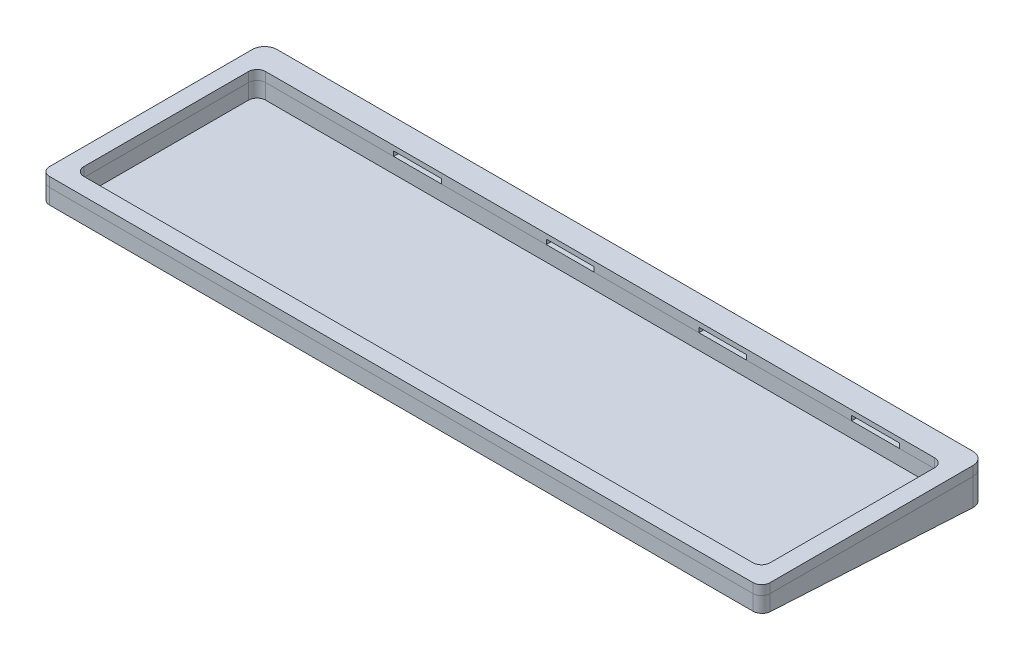
SolidWorks part; units mm, degrees
ref_plane "Front Plane" through (0, 0, 0) normal (0, 0, 1) x (1, 0, 0)
ref_plane "Top Plane" through (0, 0, 0) normal (0, 1, 0) x (1, 0, 0)
ref_plane "Right Plane" through (0, 0, 0) normal (1, 0, 0) x (0, 0, -1)
sketch "Sketch1" plane through (0, 0, 0) normal (0, 1, 0) x (1, 0, 0)
  line L0 (-179.825, 47.6224) -> (-179.825, 47.625)
  line L1 (-179.8217, 47.625) -> (179.825, 47.625)
  line L2 (-179.825, 47.6224) -> (-179.825, -47.625)
  line L3 (-179.825, -47.625) -> (179.825, -47.625)
  line L4 (179.825, 47.625) -> (179.825, -47.625)
  line L5 (-179.825, 47.625) -> (179.825, -47.625) construction
  line L6 (-179.825, -47.625) -> (179.825, 47.625) construction
  line L7 (-179.825, 47.625) -> (-179.8217, 47.625)
  circle A4 centre (157.075, 19.175) radius 1.1
  circle A5 centre (136.925, -16.775) radius 1.1
  circle A6 centre (-153.475, 33.725) radius 1.1
  circle A7 centre (17.925, 22.275) radius 1.1
  circle A8 centre (17.875, -35.075) radius 1.1
  circle A9 centre (-130.375, -35.725) radius 1.1
  point P0 (0, 0)
  dimension "D4" = 2.2
  dimension "D7" = 2.2
  dimension "D8" = 2.2
  dimension "D9" = 2.2
  dimension "D10" = 2.2
  dimension "D11" = 2.2
  dimension "D1" = 359.65
  dimension "D2" = 95.25
  dimension "D5" = 22.75
  dimension "D6" = 28.45
  dimension "D12" = 42.9
  dimension "D13" = 30.85
  dimension "D14" = 25.35
  dimension "D15" = 161.9
  dimension "D16" = 12.55
  dimension "D17" = 161.95
  dimension "D18" = 11.9
  dimension "D19" = 49.45
  dimension "D20" = 13.9
  dimension "D21" = 26.35
sketch "Sketch2" plane through (0, 0, 0) normal (0, 1, 0) x (1, 0, 0)
  line L0 (-188.825, 54.625) -> (-188.825, 60.625)
  line L1 (-188.825, 60.625) -> (-182.825, 60.625)
  line L4 (-179.825, 46.625) -> (-179.825, -46.625)
  line L5 (-178.825, -47.625) -> (178.825, -47.625)
  line L6 (179.825, 46.625) -> (179.825, -46.625)
  line L7 (-178.825, 47.625) -> (178.825, 47.625)
  line L8 (-179.825, 46.625) -> (-179.825, 47.625)
  line L9 (-182.825, 60.625) -> (188.825, 60.625)
  line L10 (-188.825, 54.625) -> (-188.825, -56.625)
  line L11 (-188.825, -56.625) -> (188.825, -56.625)
  line L12 (188.825, 60.625) -> (188.825, -56.625)
  line L13 (-179.825, 47.625) -> (-178.825, 47.625)
  line L14 (-179.825, -46.625) -> (-179.825, -47.625)
  line L15 (-179.825, -47.625) -> (-178.825, -47.625)
  line L16 (178.825, -47.625) -> (179.825, -47.625)
  line L17 (179.825, -47.625) -> (179.825, -46.625)
  line L18 (178.825, 47.625) -> (179.825, 47.625)
  line L19 (179.825, 47.625) -> (179.825, 46.625)
  circle A0 centre (157.075, 19.175) radius 1.1 construction
  circle A1 centre (136.925, -16.775) radius 1.1 construction
  circle A2 centre (17.875, -35.075) radius 1.1 construction
  circle A3 centre (17.925, 22.275) radius 1.1 construction
  circle A4 centre (-153.475, 33.725) radius 1.1 construction
  circle A5 centre (-130.375, -35.725) radius 1.1 construction
  circle A10 centre (157.075, 19.175) radius 1.1
  circle A11 centre (136.925, -16.775) radius 1.1
  circle A12 centre (17.875, -35.075) radius 1.1
  circle A13 centre (17.925, 22.275) radius 1.1
  circle A14 centre (-153.475, 33.725) radius 1.1
  circle A15 centre (-130.375, -35.725) radius 1.1
  point P30 (0, 0)
  dimension "D1" = 13
  dimension "D2" = 9
  dimension "D3" = 9
  dimension "D4" = 9
extrude "Boss-Extrude1" add sketch "Sketch2" along normal blind 13
sketch "Sketch4" plane through (0, 0, 0) normal (0, -1, 0) x (1, 0, 0)
  line L1 (-188.825, -60.625) -> (188.825, -60.625) construction
  line L3 (-188.825, 56.625) -> (188.825, 56.625) construction
  line L4 (-179.825, 47.625) -> (-179.825, -47.625)
  line L5 (179.825, 47.625) -> (-179.825, 47.625)
  line L6 (179.825, -47.625) -> (179.825, 47.625)
  line L7 (-179.825, -47.625) -> (179.825, -47.625)
  line L8 (-179.825, 47.625) -> (-179.825, -47.625)
  line L10 (179.825, -47.625) -> (179.825, 47.625)
  line L11 (-179.825, -47.625) -> (179.825, -47.625)
  line L12 (188.825, -60.625) -> (188.825, 56.625)
  line L13 (-188.825, -60.625) -> (188.825, -60.625)
  line L14 (-188.825, -60.625) -> (-188.825, 56.625)
  line L15 (-188.825, 56.625) -> (188.825, 56.625)
  line M10 (-179.825, -47.625) -> (-179.825, 47.625)
  line M12 (-179.825, 47.625) -> (179.825, 47.625)
  line M14 (179.825, 47.625) -> (179.825, -47.625)
  line M16 (179.825, -47.625) -> (-179.825, -47.625)
  line M17 (-188.825, 56.625) -> (-188.825, -60.625)
  line M19 (-188.825, -60.625) -> (188.825, -60.625)
  line M21 (188.825, -60.625) -> (188.825, 56.625)
  line M23 (188.825, 56.625) -> (-188.825, 56.625)
  dimension "D1" = 0
extrude "Boss-Extrude3" add sketch "Sketch4" along normal blind 10.5 contours M17 M19 M21 M23 M16 M10 M12 M14 | M16 M14 M12 M10 region at (0, 0, 0) region at (0, 0, -56.6707)
sketch "Sketch12" plane through (-188.825, 0, 0) normal (-1, 0, 0) x (0, 0, 1)
  line L0 (-60.625, 0) -> (56.625, 0) construction
  line L1 (-60.625, 13) -> (-60.625, -10.5) construction
  line L2 (56.625, 13) -> (56.625, -10.5) construction
  line L3 (56.625, -10.5) -> (-60.625, -10.5) construction
  line L4 (-60.625, -10.5) -> (-60.625, -6.5)
  line L5 (-60.625, -6.5) -> (56.625, 0)
  line L6 (56.625, 0) -> (56.625, -10.5)
  line L7 (56.625, -10.5) -> (-60.625, -10.5)
  dimension "D1" = 10.5
  dimension "D2" = 4
extrude "Cut-Extrude3" cut sketch "Sketch12" against normal blind 400
sketch "Sketch9" plane through (0, 0, 0) normal (0, 1, 0) x (1, 0, 0)
  line L0 (-121.9453, 45.1) -> (-108.9453, 45.1)
  line L1 (-121.9453, 31.1) -> (-108.9453, 31.1)
  line L2 (-122.4453, 44.6) -> (-122.4453, 31.6)
  line L3 (-108.4453, 44.6) -> (-108.4453, 31.6)
  line L4 (-102.8953, 45.1) -> (-89.8953, 45.1)
  line L5 (-102.8953, 31.1) -> (-89.8953, 31.1)
  line L6 (-103.3953, 44.6) -> (-103.3953, 31.6)
  line L7 (-89.3953, 44.6) -> (-89.3953, 31.6)
  line L8 (-83.8453, 45.1) -> (-70.8453, 45.1)
  line L9 (-83.8453, 31.1) -> (-70.8453, 31.1)
  line L10 (-84.3453, 44.6) -> (-84.3453, 31.6)
  line L11 (-70.3453, 44.6) -> (-70.3453, 31.6)
  line L12 (-64.7953, 45.1) -> (-51.7953, 45.1)
  line L13 (-64.7953, 31.1) -> (-51.7953, 31.1)
  line L14 (-65.2953, 44.6) -> (-65.2953, 31.6)
  line L15 (-51.2953, 44.6) -> (-51.2953, 31.6)
  line L16 (-45.7453, 45.1) -> (-32.7453, 45.1)
  line L17 (-45.7453, 31.1) -> (-32.7453, 31.1)
  line L18 (-46.2453, 44.6) -> (-46.2453, 31.6)
  line L19 (-32.2453, 44.6) -> (-32.2453, 31.6)
  line L20 (-26.6953, 45.1) -> (-13.6953, 45.1)
  line L21 (-26.6953, 31.1) -> (-13.6953, 31.1)
  line L22 (-27.1953, 44.6) -> (-27.1953, 31.6)
  line L23 (-13.1953, 44.6) -> (-13.1953, 31.6)
  line L24 (-7.6453, 45.1) -> (5.3547, 45.1)
  line L25 (-7.6453, 31.1) -> (5.3547, 31.1)
  line L26 (-8.1453, 44.6) -> (-8.1453, 31.6)
  line L27 (5.8547, 44.6) -> (5.8547, 31.6)
  line L28 (11.4047, 45.1) -> (24.4047, 45.1)
  line L29 (11.4047, 31.1) -> (24.4047, 31.1)
  line L30 (10.9047, 44.6) -> (10.9047, 31.6)
  line L31 (24.9047, 44.6) -> (24.9047, 31.6)
  line L32 (30.4547, 45.1) -> (43.4547, 45.1)
  line L33 (30.4547, 31.1) -> (43.4547, 31.1)
  line L34 (29.9547, 44.6) -> (29.9547, 31.6)
  line L35 (43.9547, 44.6) -> (43.9547, 31.6)
  line L36 (49.5047, 45.1) -> (62.5047, 45.1)
  line L37 (49.5047, 31.1) -> (62.5047, 31.1)
  line L38 (49.0047, 44.6) -> (49.0047, 31.6)
  line L39 (63.0047, 44.6) -> (63.0047, 31.6)
  line L40 (68.5547, 45.1) -> (81.5547, 45.1)
  line L41 (68.5547, 31.1) -> (81.5547, 31.1)
  line L42 (68.0547, 44.6) -> (68.0547, 31.6)
  line L43 (82.0547, 44.6) -> (82.0547, 31.6)
  line L44 (87.6047, 45.1) -> (100.6047, 45.1)
  line L45 (87.6047, 31.1) -> (100.6047, 31.1)
  line L46 (87.1047, 44.6) -> (87.1047, 31.6)
  line L47 (101.1047, 44.6) -> (101.1047, 31.6)
  line L48 (106.6547, 45.1) -> (119.6547, 45.1)
  line L49 (106.6547, 31.1) -> (119.6547, 31.1)
  line L50 (106.1547, 44.6) -> (106.1547, 31.6)
  line L51 (120.1547, 44.6) -> (120.1547, 31.6)
  line L52 (135.2297, 45.1) -> (148.2297, 45.1)
  line L53 (135.2297, 31.1) -> (148.2297, 31.1)
  line L54 (134.7297, 44.6) -> (134.7297, 31.6)
  line L55 (148.7297, 44.6) -> (148.7297, 31.6)
  line L56 (150.6677, 44.1) -> (156.6677, 44.1)
  line L57 (150.6677, 29.1) -> (156.6677, 29.1)
  line L58 (150.1677, 43.6) -> (150.1677, 29.6)
  line L59 (157.1677, 43.6) -> (157.1677, 29.6)
  line L60 (126.7917, 44.1) -> (132.7917, 44.1)
  line L61 (126.7917, 29.1) -> (132.7917, 29.1)
  line L62 (126.2917, 43.6) -> (126.2917, 29.6)
  line L63 (133.2917, 43.6) -> (133.2917, 29.6)
  line L64 (163.8047, 45.1) -> (176.8047, 45.1)
  line L65 (163.8047, 31.1) -> (176.8047, 31.1)
  line L66 (163.3047, 44.6) -> (163.3047, 31.6)
  line L67 (177.3047, 44.6) -> (177.3047, 31.6)
  line L68 (-117.1828, 26.05) -> (-104.1828, 26.05)
  line L69 (-117.1828, 12.05) -> (-104.1828, 12.05)
  line L70 (-117.6828, 25.55) -> (-117.6828, 12.55)
  line L71 (-103.6828, 25.55) -> (-103.6828, 12.55)
  line L72 (-93.3703, 26.05) -> (-80.3703, 26.05)
  line L73 (-93.3703, 12.05) -> (-80.3703, 12.05)
  line L74 (-93.8703, 25.55) -> (-93.8703, 12.55)
  line L75 (-79.8703, 25.55) -> (-79.8703, 12.55)
  line L76 (-74.3203, 26.05) -> (-61.3203, 26.05)
  line L77 (-74.3203, 12.05) -> (-61.3203, 12.05)
  line L78 (-74.8203, 25.55) -> (-74.8203, 12.55)
  line L79 (-60.8203, 25.55) -> (-60.8203, 12.55)
  line L80 (-55.2703, 26.05) -> (-42.2703, 26.05)
  line L81 (-55.2703, 12.05) -> (-42.2703, 12.05)
  line L82 (-55.7703, 25.55) -> (-55.7703, 12.55)
  line L83 (-41.7703, 25.55) -> (-41.7703, 12.55)
  line L84 (-36.2203, 26.05) -> (-23.2203, 26.05)
  line L85 (-36.2203, 12.05) -> (-23.2203, 12.05)
  line L86 (-36.7203, 25.55) -> (-36.7203, 12.55)
  line L87 (-22.7203, 25.55) -> (-22.7203, 12.55)
  line L88 (-17.1703, 26.05) -> (-4.1703, 26.05)
  line L89 (-17.1703, 12.05) -> (-4.1703, 12.05)
  line L90 (-17.6703, 25.55) -> (-17.6703, 12.55)
  line L91 (-3.6703, 25.55) -> (-3.6703, 12.55)
  line L92 (1.8797, 26.05) -> (14.8797, 26.05)
  line L93 (1.8797, 12.05) -> (14.8797, 12.05)
  line L94 (1.3797, 25.55) -> (1.3797, 12.55)
  line L95 (15.3797, 25.55) -> (15.3797, 12.55)
  line L96 (20.9297, 26.05) -> (33.9297, 26.05)
  line L97 (20.9297, 12.05) -> (33.9297, 12.05)
  line L98 (20.4297, 25.55) -> (20.4297, 12.55)
  line L99 (34.4297, 25.55) -> (34.4297, 12.55)
  line L100 (39.9797, 26.05) -> (52.9797, 26.05)
  line L101 (39.9797, 12.05) -> (52.9797, 12.05)
  line L102 (39.4797, 25.55) -> (39.4797, 12.55)
  line L103 (53.4797, 25.55) -> (53.4797, 12.55)
  line L104 (59.0297, 26.05) -> (72.0297, 26.05)
  line L105 (59.0297, 12.05) -> (72.0297, 12.05)
  line L106 (58.5297, 25.55) -> (58.5297, 12.55)
  line L107 (72.5297, 25.55) -> (72.5297, 12.55)
  line L108 (78.0797, 26.05) -> (91.0797, 26.05)
  line L109 (78.0797, 12.05) -> (91.0797, 12.05)
  line L110 (77.5797, 25.55) -> (77.5797, 12.55)
  line L111 (91.5797, 25.55) -> (91.5797, 12.55)
  line L112 (97.1297, 26.05) -> (110.1297, 26.05)
  line L113 (97.1297, 12.05) -> (110.1297, 12.05)
  line L114 (96.6297, 25.55) -> (96.6297, 12.55)
  line L115 (110.6297, 25.55) -> (110.6297, 12.55)
  line L116 (116.1797, 26.05) -> (129.1797, 26.05)
  line L117 (116.1797, 12.05) -> (129.1797, 12.05)
  line L118 (115.6797, 25.55) -> (115.6797, 12.55)
  line L119 (129.6797, 25.55) -> (129.6797, 12.55)
  line L120 (139.9922, 26.05) -> (152.9922, 26.05)
  line L121 (139.9922, 12.05) -> (152.9922, 12.05)
  line L122 (139.4922, 25.55) -> (139.4922, 12.55)
  line L123 (153.4922, 25.55) -> (153.4922, 12.55)
  line L124 (163.8047, 26.05) -> (176.8047, 26.05)
  line L125 (163.8047, 12.05) -> (176.8047, 12.05)
  line L126 (163.3047, 25.55) -> (163.3047, 12.55)
  line L127 (177.3047, 25.55) -> (177.3047, 12.55)
  line L128 (-114.8016, 7) -> (-101.8016, 7)
  line L129 (-114.8016, -7) -> (-101.8016, -7)
  line L130 (-115.3016, 6.5) -> (-115.3016, -6.5)
  line L131 (-101.3016, 6.5) -> (-101.3016, -6.5)
  line L132 (-88.6078, 7) -> (-75.6078, 7)
  line L133 (-88.6078, -7) -> (-75.6078, -7)
  line L134 (-89.1078, 6.5) -> (-89.1078, -6.5)
  line L135 (-75.1078, 6.5) -> (-75.1078, -6.5)
  line L136 (-69.5578, 7) -> (-56.5578, 7)
  line L137 (-69.5578, -7) -> (-56.5578, -7)
  line L138 (-70.0578, 6.5) -> (-70.0578, -6.5)
  line L139 (-56.0578, 6.5) -> (-56.0578, -6.5)
  line L140 (-50.5078, 7) -> (-37.5078, 7)
  line L141 (-50.5078, -7) -> (-37.5078, -7)
  line L142 (-51.0078, 6.5) -> (-51.0078, -6.5)
  line L143 (-37.0078, 6.5) -> (-37.0078, -6.5)
  line L144 (-31.4578, 7) -> (-18.4578, 7)
  line L145 (-31.4578, -7) -> (-18.4578, -7)
  line L146 (-31.9578, 6.5) -> (-31.9578, -6.5)
  line L147 (-17.9578, 6.5) -> (-17.9578, -6.5)
  line L148 (-12.4078, 7) -> (0.5922, 7)
  line L149 (-12.4078, -7) -> (0.5922, -7)
  line L150 (-12.9078, 6.5) -> (-12.9078, -6.5)
  line L151 (1.0922, 6.5) -> (1.0922, -6.5)
  line L152 (6.6422, 7) -> (19.6422, 7)
  line L153 (6.6422, -7) -> (19.6422, -7)
  line L154 (6.1422, 6.5) -> (6.1422, -6.5)
  line L155 (20.1422, 6.5) -> (20.1422, -6.5)
  line L156 (25.6922, 7) -> (38.6922, 7)
  line L157 (25.6922, -7) -> (38.6922, -7)
  line L158 (25.1922, 6.5) -> (25.1922, -6.5)
  line L159 (39.1922, 6.5) -> (39.1922, -6.5)
  line L160 (44.7422, 7) -> (57.7422, 7)
  line L161 (44.7422, -7) -> (57.7422, -7)
  line L162 (44.2422, 6.5) -> (44.2422, -6.5)
  line L163 (58.2422, 6.5) -> (58.2422, -6.5)
  line L164 (63.7922, 7) -> (76.7922, 7)
  line L165 (63.7922, -7) -> (76.7922, -7)
  line L166 (63.2922, 6.5) -> (63.2922, -6.5)
  line L167 (77.2922, 6.5) -> (77.2922, -6.5)
  line L168 (82.8422, 7) -> (95.8422, 7)
  line L169 (82.8422, -7) -> (95.8422, -7)
  line L170 (82.3422, 6.5) -> (82.3422, -6.5)
  line L171 (96.3422, 6.5) -> (96.3422, -6.5)
  line L172 (101.8922, 7) -> (114.8922, 7)
  line L173 (101.8922, -7) -> (114.8922, -7)
  line L174 (101.3922, 6.5) -> (101.3922, -6.5)
  line L175 (115.3922, 6.5) -> (115.3922, -6.5)
  line L176 (132.8484, 7) -> (145.8484, 7)
  line L177 (132.8484, -7) -> (145.8484, -7)
  line L178 (132.3484, 6.5) -> (132.3484, -6.5)
  line L179 (146.3484, 6.5) -> (146.3484, -6.5)
  line L180 (148.2864, 6) -> (154.2864, 6)
  line L181 (148.2864, -9) -> (154.2864, -9)
  line L182 (147.7864, 5.5) -> (147.7864, -8.5)
  line L183 (154.7864, 5.5) -> (154.7864, -8.5)
  line L184 (124.4104, 6) -> (130.4104, 6)
  line L185 (124.4104, -9) -> (130.4104, -9)
  line L186 (123.9104, 5.5) -> (123.9104, -8.5)
  line L187 (130.9104, 5.5) -> (130.9104, -8.5)
  line L188 (163.8047, 7) -> (176.8047, 7)
  line L189 (163.8047, -7) -> (176.8047, -7)
  line L190 (163.3047, 6.5) -> (163.3047, -6.5)
  line L191 (177.3047, 6.5) -> (177.3047, -6.5)
  line L192 (-110.0391, -12.05) -> (-97.0391, -12.05)
  line L193 (-110.0391, -26.05) -> (-97.0391, -26.05)
  line L194 (-110.5391, -12.55) -> (-110.5391, -25.55)
  line L195 (-96.5391, -12.55) -> (-96.5391, -25.55)
  line L196 (-94.6011, -13.05) -> (-88.6011, -13.05)
  line L197 (-94.6011, -28.05) -> (-88.6011, -28.05)
  line L198 (-95.1011, -13.55) -> (-95.1011, -27.55)
  line L199 (-88.1011, -13.55) -> (-88.1011, -27.55)
  line L200 (-118.4771, -13.05) -> (-112.4771, -13.05)
  line L201 (-118.4771, -28.05) -> (-112.4771, -28.05)
  line L202 (-118.9771, -13.55) -> (-118.9771, -27.55)
  line L203 (-111.9771, -13.55) -> (-111.9771, -27.55)
  line L204 (-79.0828, -12.05) -> (-66.0828, -12.05)
  line L205 (-79.0828, -26.05) -> (-66.0828, -26.05)
  line L206 (-79.5828, -12.55) -> (-79.5828, -25.55)
  line L207 (-65.5828, -12.55) -> (-65.5828, -25.55)
  line L208 (-60.0328, -12.05) -> (-47.0328, -12.05)
  line L209 (-60.0328, -26.05) -> (-47.0328, -26.05)
  line L210 (-60.5328, -12.55) -> (-60.5328, -25.55)
  line L211 (-46.5328, -12.55) -> (-46.5328, -25.55)
  line L212 (-40.9828, -12.05) -> (-27.9828, -12.05)
  line L213 (-40.9828, -26.05) -> (-27.9828, -26.05)
  line L214 (-41.4828, -12.55) -> (-41.4828, -25.55)
  line L215 (-27.4828, -12.55) -> (-27.4828, -25.55)
  line L216 (-21.9328, -12.05) -> (-8.9328, -12.05)
  line L217 (-21.9328, -26.05) -> (-8.9328, -26.05)
  line L218 (-22.4328, -12.55) -> (-22.4328, -25.55)
  line L219 (-8.4328, -12.55) -> (-8.4328, -25.55)
  line L220 (-2.8828, -12.05) -> (10.1172, -12.05)
  line L221 (-2.8828, -26.05) -> (10.1172, -26.05)
  line L222 (-3.3828, -12.55) -> (-3.3828, -25.55)
  line L223 (10.6172, -12.55) -> (10.6172, -25.55)
  line L224 (16.1672, -12.05) -> (29.1672, -12.05)
  line L225 (16.1672, -26.05) -> (29.1672, -26.05)
  line L226 (15.6672, -12.55) -> (15.6672, -25.55)
  line L227 (29.6672, -12.55) -> (29.6672, -25.55)
  line L228 (35.2172, -12.05) -> (48.2172, -12.05)
  line L229 (35.2172, -26.05) -> (48.2172, -26.05)
  line L230 (34.7172, -12.55) -> (34.7172, -25.55)
  line L231 (48.7172, -12.55) -> (48.7172, -25.55)
  line L232 (54.2672, -12.05) -> (67.2672, -12.05)
  line L233 (54.2672, -26.05) -> (67.2672, -26.05)
  line L234 (53.7672, -12.55) -> (53.7672, -25.55)
  line L235 (67.7672, -12.55) -> (67.7672, -25.55)
  line L236 (73.3172, -12.05) -> (86.3172, -12.05)
  line L237 (73.3172, -26.05) -> (86.3172, -26.05)
  line L238 (72.8172, -12.55) -> (72.8172, -25.55)
  line L239 (86.8172, -12.55) -> (86.8172, -25.55)
  line L240 (92.3672, -12.05) -> (105.3672, -12.05)
  line L241 (92.3672, -26.05) -> (105.3672, -26.05)
  line L242 (91.8672, -12.55) -> (91.8672, -25.55)
  line L243 (105.8672, -12.55) -> (105.8672, -25.55)
  line L244 (118.5609, -12.05) -> (131.5609, -12.05)
  line L245 (118.5609, -26.05) -> (131.5609, -26.05)
  line L246 (118.0609, -12.55) -> (118.0609, -25.55)
  line L247 (132.0609, -12.55) -> (132.0609, -25.55)
  line L248 (144.7547, -12.05) -> (157.7547, -12.05)
  line L249 (144.7547, -26.05) -> (157.7547, -26.05)
  line L250 (144.2547, -12.55) -> (144.2547, -25.55)
  line L251 (158.2547, -12.55) -> (158.2547, -25.55)
  line L252 (163.8047, -12.05) -> (176.8047, -12.05)
  line L253 (163.8047, -26.05) -> (176.8047, -26.05)
  line L254 (163.3047, -12.55) -> (163.3047, -25.55)
  line L255 (177.3047, -12.55) -> (177.3047, -25.55)
  line L256 (-119.5641, -31.1) -> (-106.5641, -31.1)
  line L257 (-119.5641, -45.1) -> (-106.5641, -45.1)
  line L258 (-120.0641, -31.6) -> (-120.0641, -44.6)
  line L259 (-106.0641, -31.6) -> (-106.0641, -44.6)
  line L260 (-95.7516, -31.1) -> (-82.7516, -31.1)
  line L261 (-95.7516, -45.1) -> (-82.7516, -45.1)
  line L262 (-96.2516, -31.6) -> (-96.2516, -44.6)
  line L263 (-82.2516, -31.6) -> (-82.2516, -44.6)
  line L264 (-71.9391, -31.1) -> (-58.9391, -31.1)
  line L265 (-71.9391, -45.1) -> (-58.9391, -45.1)
  line L266 (-72.4391, -31.6) -> (-72.4391, -44.6)
  line L267 (-58.4391, -31.6) -> (-58.4391, -44.6)
  line L268 (-0.5016, -31.1) -> (12.4984, -31.1)
  line L269 (-0.5016, -45.1) -> (12.4984, -45.1)
  line L270 (-1.0016, -31.6) -> (-1.0016, -44.6)
  line L271 (12.9984, -31.6) -> (12.9984, -44.6)
  line L272 (52.9984, -32.1) -> (58.9984, -32.1)
  line L273 (52.9984, -47.1) -> (58.9984, -47.1)
  line L274 (52.4984, -32.6) -> (52.4984, -46.6)
  line L275 (59.4984, -32.6) -> (59.4984, -46.6)
  line L276 (-47.0016, -32.1) -> (-41.0016, -32.1)
  line L277 (-47.0016, -47.1) -> (-41.0016, -47.1)
  line L278 (-47.5016, -32.6) -> (-47.5016, -46.6)
  line L279 (-40.5016, -32.6) -> (-40.5016, -46.6)
  line L280 (68.5547, -31.1) -> (81.5547, -31.1)
  line L281 (68.5547, -45.1) -> (81.5547, -45.1)
  line L282 (68.0547, -31.6) -> (68.0547, -44.6)
  line L283 (82.0547, -31.6) -> (82.0547, -44.6)
  line L284 (87.6047, -31.1) -> (100.6047, -31.1)
  line L285 (87.6047, -45.1) -> (100.6047, -45.1)
  line L286 (87.1047, -31.6) -> (87.1047, -44.6)
  line L287 (101.1047, -31.6) -> (101.1047, -44.6)
  line L288 (106.6547, -31.1) -> (119.6547, -31.1)
  line L289 (106.6547, -45.1) -> (119.6547, -45.1)
  line L290 (106.1547, -31.6) -> (106.1547, -44.6)
  line L291 (120.1547, -31.6) -> (120.1547, -44.6)
  line L292 (125.7047, -31.1) -> (138.7047, -31.1)
  line L293 (125.7047, -45.1) -> (138.7047, -45.1)
  line L294 (125.2047, -31.6) -> (125.2047, -44.6)
  line L295 (139.2047, -31.6) -> (139.2047, -44.6)
  line L296 (144.7547, -31.1) -> (157.7547, -31.1)
  line L297 (144.7547, -45.1) -> (157.7547, -45.1)
  line L298 (144.2547, -31.6) -> (144.2547, -44.6)
  line L299 (158.2547, -31.6) -> (158.2547, -44.6)
  line L300 (163.8047, -31.1) -> (176.8047, -31.1)
  line L301 (163.8047, -45.1) -> (176.8047, -45.1)
  line L302 (163.3047, -31.6) -> (163.3047, -44.6)
  line L303 (177.3047, -31.6) -> (177.3047, -44.6)
  line L304 (-119.9703, 47.625) -> (-103.2456, 47.625)
  line L305 (-119.9703, -47.625) -> (-100.699, -47.625)
  line L306 (-124.9703, 42.625) -> (-124.9703, -42.625)
  line L307 (179.8297, 42.625) -> (179.8297, 7.5)
  line L308 (-103.2456, 53.125) -> (-103.2456, 47.625)
  line L309 (-124.9703, 47.625) -> (-103.2456, 47.625)
  line L311 (-101.2456, 55.125) -> (-90.2456, 55.125)
  line L312 (-88.2456, 47.625) -> (-88.2456, 53.125)
  line L313 (-23.2456, 53.125) -> (-23.2456, 47.625)
  line L314 (-21.2456, 55.125) -> (-10.2456, 55.125)
  line L315 (-8.2456, 47.625) -> (-8.2456, 53.125)
  line L316 (56.7544, 53.125) -> (56.7544, 47.625)
  line L317 (58.7544, 55.125) -> (69.7544, 55.125)
  line L318 (71.7544, 47.625) -> (71.7544, 53.125)
  line L319 (136.7544, 53.125) -> (136.7544, 47.625)
  line L320 (138.7544, 55.125) -> (149.7544, 55.125)
  line L321 (151.7544, 47.625) -> (151.7544, 53.125)
  line L322 (-88.2456, 47.625) -> (-23.2456, 47.625)
  line L323 (-8.2456, 47.625) -> (56.7544, 47.625)
  line L324 (71.7544, 47.625) -> (136.7544, 47.625)
  line L325 (151.7544, 47.625) -> (174.8297, 47.625)
  line L326 (-20.699, -47.625) -> (-20.699, -52.625)
  line L327 (-5.699, -47.625) -> (-5.699, -52.625)
  line L329 (-100.699, -47.625) -> (-100.699, -52.625)
  line L330 (-98.699, -54.625) -> (-87.699, -54.625)
  line L331 (-85.699, -47.625) -> (-85.699, -52.625)
  line L332 (-18.699, -54.625) -> (-7.699, -54.625)
  line L333 (59.301, -47.625) -> (59.301, -52.625)
  line L334 (74.301, -47.625) -> (74.301, -52.625)
  line L335 (61.301, -54.625) -> (72.301, -54.625)
  line L336 (139.301, -47.625) -> (139.301, -52.625)
  line L337 (154.301, -47.625) -> (154.301, -52.625)
  line L338 (141.301, -54.625) -> (152.301, -54.625)
  line L339 (-85.699, -47.625) -> (-20.699, -47.625)
  line L340 (-5.699, -47.625) -> (59.301, -47.625)
  line L341 (74.301, -47.625) -> (139.301, -47.625)
  line L342 (154.301, -47.625) -> (174.8297, -47.625)
  line L343 (179.8297, -7.5) -> (179.8297, -42.625)
  line L348 (179.8297, 7.5) -> (179.8297, -7.5)
  arc A0 (-121.9453, 45.1) -> (-122.4453, 44.6) centre (-121.9453, 44.6) ccw
  arc A1 (-108.4453, 44.6) -> (-108.9453, 45.1) centre (-108.9453, 44.6) ccw
  arc A2 (-122.4453, 31.6) -> (-121.9453, 31.1) centre (-121.9453, 31.6) ccw
  arc A3 (-108.9453, 31.1) -> (-108.4453, 31.6) centre (-108.9453, 31.6) ccw
  arc A4 (-102.8953, 45.1) -> (-103.3953, 44.6) centre (-102.8953, 44.6) ccw
  arc A5 (-89.3953, 44.6) -> (-89.8953, 45.1) centre (-89.8953, 44.6) ccw
  arc A6 (-103.3953, 31.6) -> (-102.8953, 31.1) centre (-102.8953, 31.6) ccw
  arc A7 (-89.8953, 31.1) -> (-89.3953, 31.6) centre (-89.8953, 31.6) ccw
  arc A8 (-83.8453, 45.1) -> (-84.3453, 44.6) centre (-83.8453, 44.6) ccw
  arc A9 (-70.3453, 44.6) -> (-70.8453, 45.1) centre (-70.8453, 44.6) ccw
  arc A10 (-84.3453, 31.6) -> (-83.8453, 31.1) centre (-83.8453, 31.6) ccw
  arc A11 (-70.8453, 31.1) -> (-70.3453, 31.6) centre (-70.8453, 31.6) ccw
  arc A12 (-64.7953, 45.1) -> (-65.2953, 44.6) centre (-64.7953, 44.6) ccw
  arc A13 (-51.2953, 44.6) -> (-51.7953, 45.1) centre (-51.7953, 44.6) ccw
  arc A14 (-65.2953, 31.6) -> (-64.7953, 31.1) centre (-64.7953, 31.6) ccw
  arc A15 (-51.7953, 31.1) -> (-51.2953, 31.6) centre (-51.7953, 31.6) ccw
  arc A16 (-45.7453, 45.1) -> (-46.2453, 44.6) centre (-45.7453, 44.6) ccw
  arc A17 (-32.2453, 44.6) -> (-32.7453, 45.1) centre (-32.7453, 44.6) ccw
  arc A18 (-46.2453, 31.6) -> (-45.7453, 31.1) centre (-45.7453, 31.6) ccw
  arc A19 (-32.7453, 31.1) -> (-32.2453, 31.6) centre (-32.7453, 31.6) ccw
  arc A20 (-26.6953, 45.1) -> (-27.1953, 44.6) centre (-26.6953, 44.6) ccw
  arc A21 (-13.1953, 44.6) -> (-13.6953, 45.1) centre (-13.6953, 44.6) ccw
  arc A22 (-27.1953, 31.6) -> (-26.6953, 31.1) centre (-26.6953, 31.6) ccw
  arc A23 (-13.6953, 31.1) -> (-13.1953, 31.6) centre (-13.6953, 31.6) ccw
  arc A24 (-7.6453, 45.1) -> (-8.1453, 44.6) centre (-7.6453, 44.6) ccw
  arc A25 (5.8547, 44.6) -> (5.3547, 45.1) centre (5.3547, 44.6) ccw
  arc A26 (-8.1453, 31.6) -> (-7.6453, 31.1) centre (-7.6453, 31.6) ccw
  arc A27 (5.3547, 31.1) -> (5.8547, 31.6) centre (5.3547, 31.6) ccw
  arc A28 (11.4047, 45.1) -> (10.9047, 44.6) centre (11.4047, 44.6) ccw
  arc A29 (24.9047, 44.6) -> (24.4047, 45.1) centre (24.4047, 44.6) ccw
  arc A30 (10.9047, 31.6) -> (11.4047, 31.1) centre (11.4047, 31.6) ccw
  arc A31 (24.4047, 31.1) -> (24.9047, 31.6) centre (24.4047, 31.6) ccw
  arc A32 (30.4547, 45.1) -> (29.9547, 44.6) centre (30.4547, 44.6) ccw
  arc A33 (43.9547, 44.6) -> (43.4547, 45.1) centre (43.4547, 44.6) ccw
  arc A34 (29.9547, 31.6) -> (30.4547, 31.1) centre (30.4547, 31.6) ccw
  arc A35 (43.4547, 31.1) -> (43.9547, 31.6) centre (43.4547, 31.6) ccw
  arc A36 (49.5047, 45.1) -> (49.0047, 44.6) centre (49.5047, 44.6) ccw
  arc A37 (63.0047, 44.6) -> (62.5047, 45.1) centre (62.5047, 44.6) ccw
  arc A38 (49.0047, 31.6) -> (49.5047, 31.1) centre (49.5047, 31.6) ccw
  arc A39 (62.5047, 31.1) -> (63.0047, 31.6) centre (62.5047, 31.6) ccw
  arc A40 (68.5547, 45.1) -> (68.0547, 44.6) centre (68.5547, 44.6) ccw
  arc A41 (82.0547, 44.6) -> (81.5547, 45.1) centre (81.5547, 44.6) ccw
  arc A42 (68.0547, 31.6) -> (68.5547, 31.1) centre (68.5547, 31.6) ccw
  arc A43 (81.5547, 31.1) -> (82.0547, 31.6) centre (81.5547, 31.6) ccw
  arc A44 (87.6047, 45.1) -> (87.1047, 44.6) centre (87.6047, 44.6) ccw
  arc A45 (101.1047, 44.6) -> (100.6047, 45.1) centre (100.6047, 44.6) ccw
  arc A46 (87.1047, 31.6) -> (87.6047, 31.1) centre (87.6047, 31.6) ccw
  arc A47 (100.6047, 31.1) -> (101.1047, 31.6) centre (100.6047, 31.6) ccw
  arc A48 (106.6547, 45.1) -> (106.1547, 44.6) centre (106.6547, 44.6) ccw
  arc A49 (120.1547, 44.6) -> (119.6547, 45.1) centre (119.6547, 44.6) ccw
  arc A50 (106.1547, 31.6) -> (106.6547, 31.1) centre (106.6547, 31.6) ccw
  arc A51 (119.6547, 31.1) -> (120.1547, 31.6) centre (119.6547, 31.6) ccw
  arc A52 (135.2297, 45.1) -> (134.7297, 44.6) centre (135.2297, 44.6) ccw
  arc A53 (148.7297, 44.6) -> (148.2297, 45.1) centre (148.2297, 44.6) ccw
  arc A54 (134.7297, 31.6) -> (135.2297, 31.1) centre (135.2297, 31.6) ccw
  arc A55 (148.2297, 31.1) -> (148.7297, 31.6) centre (148.2297, 31.6) ccw
  arc A56 (150.6677, 44.1) -> (150.1677, 43.6) centre (150.6677, 43.6) ccw
  arc A57 (157.1677, 43.6) -> (156.6677, 44.1) centre (156.6677, 43.6) ccw
  arc A58 (150.1677, 29.6) -> (150.6677, 29.1) centre (150.6677, 29.6) ccw
  arc A59 (156.6677, 29.1) -> (157.1677, 29.6) centre (156.6677, 29.6) ccw
  arc A60 (126.7917, 44.1) -> (126.2917, 43.6) centre (126.7917, 43.6) ccw
  arc A61 (133.2917, 43.6) -> (132.7917, 44.1) centre (132.7917, 43.6) ccw
  arc A62 (126.2917, 29.6) -> (126.7917, 29.1) centre (126.7917, 29.6) ccw
  arc A63 (132.7917, 29.1) -> (133.2917, 29.6) centre (132.7917, 29.6) ccw
  arc A64 (163.8047, 45.1) -> (163.3047, 44.6) centre (163.8047, 44.6) ccw
  arc A65 (177.3047, 44.6) -> (176.8047, 45.1) centre (176.8047, 44.6) ccw
  arc A66 (163.3047, 31.6) -> (163.8047, 31.1) centre (163.8047, 31.6) ccw
  arc A67 (176.8047, 31.1) -> (177.3047, 31.6) centre (176.8047, 31.6) ccw
  arc A68 (-117.1828, 26.05) -> (-117.6828, 25.55) centre (-117.1828, 25.55) ccw
  arc A69 (-103.6828, 25.55) -> (-104.1828, 26.05) centre (-104.1828, 25.55) ccw
  arc A70 (-117.6828, 12.55) -> (-117.1828, 12.05) centre (-117.1828, 12.55) ccw
  arc A71 (-104.1828, 12.05) -> (-103.6828, 12.55) centre (-104.1828, 12.55) ccw
  arc A72 (-93.3703, 26.05) -> (-93.8703, 25.55) centre (-93.3703, 25.55) ccw
  arc A73 (-79.8703, 25.55) -> (-80.3703, 26.05) centre (-80.3703, 25.55) ccw
  arc A74 (-93.8703, 12.55) -> (-93.3703, 12.05) centre (-93.3703, 12.55) ccw
  arc A75 (-80.3703, 12.05) -> (-79.8703, 12.55) centre (-80.3703, 12.55) ccw
  arc A76 (-74.3203, 26.05) -> (-74.8203, 25.55) centre (-74.3203, 25.55) ccw
  arc A77 (-60.8203, 25.55) -> (-61.3203, 26.05) centre (-61.3203, 25.55) ccw
  arc A78 (-74.8203, 12.55) -> (-74.3203, 12.05) centre (-74.3203, 12.55) ccw
  arc A79 (-61.3203, 12.05) -> (-60.8203, 12.55) centre (-61.3203, 12.55) ccw
  arc A80 (-55.2703, 26.05) -> (-55.7703, 25.55) centre (-55.2703, 25.55) ccw
  arc A81 (-41.7703, 25.55) -> (-42.2703, 26.05) centre (-42.2703, 25.55) ccw
  arc A82 (-55.7703, 12.55) -> (-55.2703, 12.05) centre (-55.2703, 12.55) ccw
  arc A83 (-42.2703, 12.05) -> (-41.7703, 12.55) centre (-42.2703, 12.55) ccw
  arc A84 (-36.2203, 26.05) -> (-36.7203, 25.55) centre (-36.2203, 25.55) ccw
  arc A85 (-22.7203, 25.55) -> (-23.2203, 26.05) centre (-23.2203, 25.55) ccw
  arc A86 (-36.7203, 12.55) -> (-36.2203, 12.05) centre (-36.2203, 12.55) ccw
  arc A87 (-23.2203, 12.05) -> (-22.7203, 12.55) centre (-23.2203, 12.55) ccw
  arc A88 (-17.1703, 26.05) -> (-17.6703, 25.55) centre (-17.1703, 25.55) ccw
  arc A89 (-3.6703, 25.55) -> (-4.1703, 26.05) centre (-4.1703, 25.55) ccw
  arc A90 (-17.6703, 12.55) -> (-17.1703, 12.05) centre (-17.1703, 12.55) ccw
  arc A91 (-4.1703, 12.05) -> (-3.6703, 12.55) centre (-4.1703, 12.55) ccw
  arc A92 (1.8797, 26.05) -> (1.3797, 25.55) centre (1.8797, 25.55) ccw
  arc A93 (15.3797, 25.55) -> (14.8797, 26.05) centre (14.8797, 25.55) ccw
  arc A94 (1.3797, 12.55) -> (1.8797, 12.05) centre (1.8797, 12.55) ccw
  arc A95 (14.8797, 12.05) -> (15.3797, 12.55) centre (14.8797, 12.55) ccw
  arc A96 (20.9297, 26.05) -> (20.4297, 25.55) centre (20.9297, 25.55) ccw
  arc A97 (34.4297, 25.55) -> (33.9297, 26.05) centre (33.9297, 25.55) ccw
  arc A98 (20.4297, 12.55) -> (20.9297, 12.05) centre (20.9297, 12.55) ccw
  arc A99 (33.9297, 12.05) -> (34.4297, 12.55) centre (33.9297, 12.55) ccw
  arc A100 (39.9797, 26.05) -> (39.4797, 25.55) centre (39.9797, 25.55) ccw
  arc A101 (53.4797, 25.55) -> (52.9797, 26.05) centre (52.9797, 25.55) ccw
  arc A102 (39.4797, 12.55) -> (39.9797, 12.05) centre (39.9797, 12.55) ccw
  arc A103 (52.9797, 12.05) -> (53.4797, 12.55) centre (52.9797, 12.55) ccw
  arc A104 (59.0297, 26.05) -> (58.5297, 25.55) centre (59.0297, 25.55) ccw
  arc A105 (72.5297, 25.55) -> (72.0297, 26.05) centre (72.0297, 25.55) ccw
  arc A106 (58.5297, 12.55) -> (59.0297, 12.05) centre (59.0297, 12.55) ccw
  arc A107 (72.0297, 12.05) -> (72.5297, 12.55) centre (72.0297, 12.55) ccw
  arc A108 (78.0797, 26.05) -> (77.5797, 25.55) centre (78.0797, 25.55) ccw
  arc A109 (91.5797, 25.55) -> (91.0797, 26.05) centre (91.0797, 25.55) ccw
  arc A110 (77.5797, 12.55) -> (78.0797, 12.05) centre (78.0797, 12.55) ccw
  arc A111 (91.0797, 12.05) -> (91.5797, 12.55) centre (91.0797, 12.55) ccw
  arc A112 (97.1297, 26.05) -> (96.6297, 25.55) centre (97.1297, 25.55) ccw
  arc A113 (110.6297, 25.55) -> (110.1297, 26.05) centre (110.1297, 25.55) ccw
  arc A114 (96.6297, 12.55) -> (97.1297, 12.05) centre (97.1297, 12.55) ccw
  arc A115 (110.1297, 12.05) -> (110.6297, 12.55) centre (110.1297, 12.55) ccw
  arc A116 (116.1797, 26.05) -> (115.6797, 25.55) centre (116.1797, 25.55) ccw
  arc A117 (129.6797, 25.55) -> (129.1797, 26.05) centre (129.1797, 25.55) ccw
  arc A118 (115.6797, 12.55) -> (116.1797, 12.05) centre (116.1797, 12.55) ccw
  arc A119 (129.1797, 12.05) -> (129.6797, 12.55) centre (129.1797, 12.55) ccw
  arc A120 (139.9922, 26.05) -> (139.4922, 25.55) centre (139.9922, 25.55) ccw
  arc A121 (153.4922, 25.55) -> (152.9922, 26.05) centre (152.9922, 25.55) ccw
  arc A122 (139.4922, 12.55) -> (139.9922, 12.05) centre (139.9922, 12.55) ccw
  arc A123 (152.9922, 12.05) -> (153.4922, 12.55) centre (152.9922, 12.55) ccw
  arc A124 (163.8047, 26.05) -> (163.3047, 25.55) centre (163.8047, 25.55) ccw
  arc A125 (177.3047, 25.55) -> (176.8047, 26.05) centre (176.8047, 25.55) ccw
  arc A126 (163.3047, 12.55) -> (163.8047, 12.05) centre (163.8047, 12.55) ccw
  arc A127 (176.8047, 12.05) -> (177.3047, 12.55) centre (176.8047, 12.55) ccw
  arc A128 (-114.8016, 7) -> (-115.3016, 6.5) centre (-114.8016, 6.5) ccw
  arc A129 (-101.3016, 6.5) -> (-101.8016, 7) centre (-101.8016, 6.5) ccw
  arc A130 (-115.3016, -6.5) -> (-114.8016, -7) centre (-114.8016, -6.5) ccw
  arc A131 (-101.8016, -7) -> (-101.3016, -6.5) centre (-101.8016, -6.5) ccw
  arc A132 (-88.6078, 7) -> (-89.1078, 6.5) centre (-88.6078, 6.5) ccw
  arc A133 (-75.1078, 6.5) -> (-75.6078, 7) centre (-75.6078, 6.5) ccw
  arc A134 (-89.1078, -6.5) -> (-88.6078, -7) centre (-88.6078, -6.5) ccw
  arc A135 (-75.6078, -7) -> (-75.1078, -6.5) centre (-75.6078, -6.5) ccw
  arc A136 (-69.5578, 7) -> (-70.0578, 6.5) centre (-69.5578, 6.5) ccw
  arc A137 (-56.0578, 6.5) -> (-56.5578, 7) centre (-56.5578, 6.5) ccw
  arc A138 (-70.0578, -6.5) -> (-69.5578, -7) centre (-69.5578, -6.5) ccw
  arc A139 (-56.5578, -7) -> (-56.0578, -6.5) centre (-56.5578, -6.5) ccw
  arc A140 (-50.5078, 7) -> (-51.0078, 6.5) centre (-50.5078, 6.5) ccw
  arc A141 (-37.0078, 6.5) -> (-37.5078, 7) centre (-37.5078, 6.5) ccw
  arc A142 (-51.0078, -6.5) -> (-50.5078, -7) centre (-50.5078, -6.5) ccw
  arc A143 (-37.5078, -7) -> (-37.0078, -6.5) centre (-37.5078, -6.5) ccw
  arc A144 (-31.4578, 7) -> (-31.9578, 6.5) centre (-31.4578, 6.5) ccw
  arc A145 (-17.9578, 6.5) -> (-18.4578, 7) centre (-18.4578, 6.5) ccw
  arc A146 (-31.9578, -6.5) -> (-31.4578, -7) centre (-31.4578, -6.5) ccw
  arc A147 (-18.4578, -7) -> (-17.9578, -6.5) centre (-18.4578, -6.5) ccw
  arc A148 (-12.4078, 7) -> (-12.9078, 6.5) centre (-12.4078, 6.5) ccw
  arc A149 (1.0922, 6.5) -> (0.5922, 7) centre (0.5922, 6.5) ccw
  arc A150 (-12.9078, -6.5) -> (-12.4078, -7) centre (-12.4078, -6.5) ccw
  arc A151 (0.5922, -7) -> (1.0922, -6.5) centre (0.5922, -6.5) ccw
  arc A152 (6.6422, 7) -> (6.1422, 6.5) centre (6.6422, 6.5) ccw
  arc A153 (20.1422, 6.5) -> (19.6422, 7) centre (19.6422, 6.5) ccw
  arc A154 (6.1422, -6.5) -> (6.6422, -7) centre (6.6422, -6.5) ccw
  arc A155 (19.6422, -7) -> (20.1422, -6.5) centre (19.6422, -6.5) ccw
  arc A156 (25.6922, 7) -> (25.1922, 6.5) centre (25.6922, 6.5) ccw
  arc A157 (39.1922, 6.5) -> (38.6922, 7) centre (38.6922, 6.5) ccw
  arc A158 (25.1922, -6.5) -> (25.6922, -7) centre (25.6922, -6.5) ccw
  arc A159 (38.6922, -7) -> (39.1922, -6.5) centre (38.6922, -6.5) ccw
  arc A160 (44.7422, 7) -> (44.2422, 6.5) centre (44.7422, 6.5) ccw
  arc A161 (58.2422, 6.5) -> (57.7422, 7) centre (57.7422, 6.5) ccw
  arc A162 (44.2422, -6.5) -> (44.7422, -7) centre (44.7422, -6.5) ccw
  arc A163 (57.7422, -7) -> (58.2422, -6.5) centre (57.7422, -6.5) ccw
  arc A164 (63.7922, 7) -> (63.2922, 6.5) centre (63.7922, 6.5) ccw
  arc A165 (77.2922, 6.5) -> (76.7922, 7) centre (76.7922, 6.5) ccw
  arc A166 (63.2922, -6.5) -> (63.7922, -7) centre (63.7922, -6.5) ccw
  arc A167 (76.7922, -7) -> (77.2922, -6.5) centre (76.7922, -6.5) ccw
  arc A168 (82.8422, 7) -> (82.3422, 6.5) centre (82.8422, 6.5) ccw
  arc A169 (96.3422, 6.5) -> (95.8422, 7) centre (95.8422, 6.5) ccw
  arc A170 (82.3422, -6.5) -> (82.8422, -7) centre (82.8422, -6.5) ccw
  arc A171 (95.8422, -7) -> (96.3422, -6.5) centre (95.8422, -6.5) ccw
  arc A172 (101.8922, 7) -> (101.3922, 6.5) centre (101.8922, 6.5) ccw
  arc A173 (115.3922, 6.5) -> (114.8922, 7) centre (114.8922, 6.5) ccw
  arc A174 (101.3922, -6.5) -> (101.8922, -7) centre (101.8922, -6.5) ccw
  arc A175 (114.8922, -7) -> (115.3922, -6.5) centre (114.8922, -6.5) ccw
  arc A176 (132.8484, 7) -> (132.3484, 6.5) centre (132.8484, 6.5) ccw
  arc A177 (146.3484, 6.5) -> (145.8484, 7) centre (145.8484, 6.5) ccw
  arc A178 (132.3484, -6.5) -> (132.8484, -7) centre (132.8484, -6.5) ccw
  arc A179 (145.8484, -7) -> (146.3484, -6.5) centre (145.8484, -6.5) ccw
  arc A180 (148.2864, 6) -> (147.7864, 5.5) centre (148.2864, 5.5) ccw
  arc A181 (154.7864, 5.5) -> (154.2864, 6) centre (154.2864, 5.5) ccw
  arc A182 (147.7864, -8.5) -> (148.2864, -9) centre (148.2864, -8.5) ccw
  arc A183 (154.2864, -9) -> (154.7864, -8.5) centre (154.2864, -8.5) ccw
  arc A184 (124.4104, 6) -> (123.9104, 5.5) centre (124.4104, 5.5) ccw
  arc A185 (130.9104, 5.5) -> (130.4104, 6) centre (130.4104, 5.5) ccw
  arc A186 (123.9104, -8.5) -> (124.4104, -9) centre (124.4104, -8.5) ccw
  arc A187 (130.4104, -9) -> (130.9104, -8.5) centre (130.4104, -8.5) ccw
  arc A188 (163.8047, 7) -> (163.3047, 6.5) centre (163.8047, 6.5) ccw
  arc A189 (177.3047, 6.5) -> (176.8047, 7) centre (176.8047, 6.5) ccw
  arc A190 (163.3047, -6.5) -> (163.8047, -7) centre (163.8047, -6.5) ccw
  arc A191 (176.8047, -7) -> (177.3047, -6.5) centre (176.8047, -6.5) ccw
  arc A192 (-110.0391, -12.05) -> (-110.5391, -12.55) centre (-110.0391, -12.55) ccw
  arc A193 (-96.5391, -12.55) -> (-97.0391, -12.05) centre (-97.0391, -12.55) ccw
  arc A194 (-110.5391, -25.55) -> (-110.0391, -26.05) centre (-110.0391, -25.55) ccw
  arc A195 (-97.0391, -26.05) -> (-96.5391, -25.55) centre (-97.0391, -25.55) ccw
  arc A196 (-94.6011, -13.05) -> (-95.1011, -13.55) centre (-94.6011, -13.55) ccw
  arc A197 (-88.1011, -13.55) -> (-88.6011, -13.05) centre (-88.6011, -13.55) ccw
  arc A198 (-95.1011, -27.55) -> (-94.6011, -28.05) centre (-94.6011, -27.55) ccw
  arc A199 (-88.6011, -28.05) -> (-88.1011, -27.55) centre (-88.6011, -27.55) ccw
  arc A200 (-118.4771, -13.05) -> (-118.9771, -13.55) centre (-118.4771, -13.55) ccw
  arc A201 (-111.9771, -13.55) -> (-112.4771, -13.05) centre (-112.4771, -13.55) ccw
  arc A202 (-118.9771, -27.55) -> (-118.4771, -28.05) centre (-118.4771, -27.55) ccw
  arc A203 (-112.4771, -28.05) -> (-111.9771, -27.55) centre (-112.4771, -27.55) ccw
  arc A204 (-79.0828, -12.05) -> (-79.5828, -12.55) centre (-79.0828, -12.55) ccw
  arc A205 (-65.5828, -12.55) -> (-66.0828, -12.05) centre (-66.0828, -12.55) ccw
  arc A206 (-79.5828, -25.55) -> (-79.0828, -26.05) centre (-79.0828, -25.55) ccw
  arc A207 (-66.0828, -26.05) -> (-65.5828, -25.55) centre (-66.0828, -25.55) ccw
  arc A208 (-60.0328, -12.05) -> (-60.5328, -12.55) centre (-60.0328, -12.55) ccw
  arc A209 (-46.5328, -12.55) -> (-47.0328, -12.05) centre (-47.0328, -12.55) ccw
  arc A210 (-60.5328, -25.55) -> (-60.0328, -26.05) centre (-60.0328, -25.55) ccw
  arc A211 (-47.0328, -26.05) -> (-46.5328, -25.55) centre (-47.0328, -25.55) ccw
  arc A212 (-40.9828, -12.05) -> (-41.4828, -12.55) centre (-40.9828, -12.55) ccw
  arc A213 (-27.4828, -12.55) -> (-27.9828, -12.05) centre (-27.9828, -12.55) ccw
  arc A214 (-41.4828, -25.55) -> (-40.9828, -26.05) centre (-40.9828, -25.55) ccw
  arc A215 (-27.9828, -26.05) -> (-27.4828, -25.55) centre (-27.9828, -25.55) ccw
  arc A216 (-21.9328, -12.05) -> (-22.4328, -12.55) centre (-21.9328, -12.55) ccw
  arc A217 (-8.4328, -12.55) -> (-8.9328, -12.05) centre (-8.9328, -12.55) ccw
  arc A218 (-22.4328, -25.55) -> (-21.9328, -26.05) centre (-21.9328, -25.55) ccw
  arc A219 (-8.9328, -26.05) -> (-8.4328, -25.55) centre (-8.9328, -25.55) ccw
  arc A220 (-2.8828, -12.05) -> (-3.3828, -12.55) centre (-2.8828, -12.55) ccw
  arc A221 (10.6172, -12.55) -> (10.1172, -12.05) centre (10.1172, -12.55) ccw
  arc A222 (-3.3828, -25.55) -> (-2.8828, -26.05) centre (-2.8828, -25.55) ccw
  arc A223 (10.1172, -26.05) -> (10.6172, -25.55) centre (10.1172, -25.55) ccw
  arc A224 (16.1672, -12.05) -> (15.6672, -12.55) centre (16.1672, -12.55) ccw
  arc A225 (29.6672, -12.55) -> (29.1672, -12.05) centre (29.1672, -12.55) ccw
  arc A226 (15.6672, -25.55) -> (16.1672, -26.05) centre (16.1672, -25.55) ccw
  arc A227 (29.1672, -26.05) -> (29.6672, -25.55) centre (29.1672, -25.55) ccw
  arc A228 (35.2172, -12.05) -> (34.7172, -12.55) centre (35.2172, -12.55) ccw
  arc A229 (48.7172, -12.55) -> (48.2172, -12.05) centre (48.2172, -12.55) ccw
  arc A230 (34.7172, -25.55) -> (35.2172, -26.05) centre (35.2172, -25.55) ccw
  arc A231 (48.2172, -26.05) -> (48.7172, -25.55) centre (48.2172, -25.55) ccw
  arc A232 (54.2672, -12.05) -> (53.7672, -12.55) centre (54.2672, -12.55) ccw
  arc A233 (67.7672, -12.55) -> (67.2672, -12.05) centre (67.2672, -12.55) ccw
  arc A234 (53.7672, -25.55) -> (54.2672, -26.05) centre (54.2672, -25.55) ccw
  arc A235 (67.2672, -26.05) -> (67.7672, -25.55) centre (67.2672, -25.55) ccw
  arc A236 (73.3172, -12.05) -> (72.8172, -12.55) centre (73.3172, -12.55) ccw
  arc A237 (86.8172, -12.55) -> (86.3172, -12.05) centre (86.3172, -12.55) ccw
  arc A238 (72.8172, -25.55) -> (73.3172, -26.05) centre (73.3172, -25.55) ccw
  arc A239 (86.3172, -26.05) -> (86.8172, -25.55) centre (86.3172, -25.55) ccw
  arc A240 (92.3672, -12.05) -> (91.8672, -12.55) centre (92.3672, -12.55) ccw
  arc A241 (105.8672, -12.55) -> (105.3672, -12.05) centre (105.3672, -12.55) ccw
  arc A242 (91.8672, -25.55) -> (92.3672, -26.05) centre (92.3672, -25.55) ccw
  arc A243 (105.3672, -26.05) -> (105.8672, -25.55) centre (105.3672, -25.55) ccw
  arc A244 (118.5609, -12.05) -> (118.0609, -12.55) centre (118.5609, -12.55) ccw
  arc A245 (132.0609, -12.55) -> (131.5609, -12.05) centre (131.5609, -12.55) ccw
  arc A246 (118.0609, -25.55) -> (118.5609, -26.05) centre (118.5609, -25.55) ccw
  arc A247 (131.5609, -26.05) -> (132.0609, -25.55) centre (131.5609, -25.55) ccw
  arc A248 (144.7547, -12.05) -> (144.2547, -12.55) centre (144.7547, -12.55) ccw
  arc A249 (158.2547, -12.55) -> (157.7547, -12.05) centre (157.7547, -12.55) ccw
  arc A250 (144.2547, -25.55) -> (144.7547, -26.05) centre (144.7547, -25.55) ccw
  arc A251 (157.7547, -26.05) -> (158.2547, -25.55) centre (157.7547, -25.55) ccw
  arc A252 (163.8047, -12.05) -> (163.3047, -12.55) centre (163.8047, -12.55) ccw
  arc A253 (177.3047, -12.55) -> (176.8047, -12.05) centre (176.8047, -12.55) ccw
  arc A254 (163.3047, -25.55) -> (163.8047, -26.05) centre (163.8047, -25.55) ccw
  arc A255 (176.8047, -26.05) -> (177.3047, -25.55) centre (176.8047, -25.55) ccw
  arc A256 (-119.5641, -31.1) -> (-120.0641, -31.6) centre (-119.5641, -31.6) ccw
  arc A257 (-106.0641, -31.6) -> (-106.5641, -31.1) centre (-106.5641, -31.6) ccw
  arc A258 (-120.0641, -44.6) -> (-119.5641, -45.1) centre (-119.5641, -44.6) ccw
  arc A259 (-106.5641, -45.1) -> (-106.0641, -44.6) centre (-106.5641, -44.6) ccw
  arc A260 (-95.7516, -31.1) -> (-96.2516, -31.6) centre (-95.7516, -31.6) ccw
  arc A261 (-82.2516, -31.6) -> (-82.7516, -31.1) centre (-82.7516, -31.6) ccw
  arc A262 (-96.2516, -44.6) -> (-95.7516, -45.1) centre (-95.7516, -44.6) ccw
  arc A263 (-82.7516, -45.1) -> (-82.2516, -44.6) centre (-82.7516, -44.6) ccw
  arc A264 (-71.9391, -31.1) -> (-72.4391, -31.6) centre (-71.9391, -31.6) ccw
  arc A265 (-58.4391, -31.6) -> (-58.9391, -31.1) centre (-58.9391, -31.6) ccw
  arc A266 (-72.4391, -44.6) -> (-71.9391, -45.1) centre (-71.9391, -44.6) ccw
  arc A267 (-58.9391, -45.1) -> (-58.4391, -44.6) centre (-58.9391, -44.6) ccw
  arc A268 (-0.5016, -31.1) -> (-1.0016, -31.6) centre (-0.5016, -31.6) ccw
  arc A269 (12.9984, -31.6) -> (12.4984, -31.1) centre (12.4984, -31.6) ccw
  arc A270 (-1.0016, -44.6) -> (-0.5016, -45.1) centre (-0.5016, -44.6) ccw
  arc A271 (12.4984, -45.1) -> (12.9984, -44.6) centre (12.4984, -44.6) ccw
  arc A272 (52.9984, -32.1) -> (52.4984, -32.6) centre (52.9984, -32.6) ccw
  arc A273 (59.4984, -32.6) -> (58.9984, -32.1) centre (58.9984, -32.6) ccw
  arc A274 (52.4984, -46.6) -> (52.9984, -47.1) centre (52.9984, -46.6) ccw
  arc A275 (58.9984, -47.1) -> (59.4984, -46.6) centre (58.9984, -46.6) ccw
  arc A276 (-47.0016, -32.1) -> (-47.5016, -32.6) centre (-47.0016, -32.6) ccw
  arc A277 (-40.5016, -32.6) -> (-41.0016, -32.1) centre (-41.0016, -32.6) ccw
  arc A278 (-47.5016, -46.6) -> (-47.0016, -47.1) centre (-47.0016, -46.6) ccw
  arc A279 (-41.0016, -47.1) -> (-40.5016, -46.6) centre (-41.0016, -46.6) ccw
  arc A280 (68.5547, -31.1) -> (68.0547, -31.6) centre (68.5547, -31.6) ccw
  arc A281 (82.0547, -31.6) -> (81.5547, -31.1) centre (81.5547, -31.6) ccw
  arc A282 (68.0547, -44.6) -> (68.5547, -45.1) centre (68.5547, -44.6) ccw
  arc A283 (81.5547, -45.1) -> (82.0547, -44.6) centre (81.5547, -44.6) ccw
  arc A284 (87.6047, -31.1) -> (87.1047, -31.6) centre (87.6047, -31.6) ccw
  arc A285 (101.1047, -31.6) -> (100.6047, -31.1) centre (100.6047, -31.6) ccw
  arc A286 (87.1047, -44.6) -> (87.6047, -45.1) centre (87.6047, -44.6) ccw
  arc A287 (100.6047, -45.1) -> (101.1047, -44.6) centre (100.6047, -44.6) ccw
  arc A288 (106.6547, -31.1) -> (106.1547, -31.6) centre (106.6547, -31.6) ccw
  arc A289 (120.1547, -31.6) -> (119.6547, -31.1) centre (119.6547, -31.6) ccw
  arc A290 (106.1547, -44.6) -> (106.6547, -45.1) centre (106.6547, -44.6) ccw
  arc A291 (119.6547, -45.1) -> (120.1547, -44.6) centre (119.6547, -44.6) ccw
  arc A292 (125.7047, -31.1) -> (125.2047, -31.6) centre (125.7047, -31.6) ccw
  arc A293 (139.2047, -31.6) -> (138.7047, -31.1) centre (138.7047, -31.6) ccw
  arc A294 (125.2047, -44.6) -> (125.7047, -45.1) centre (125.7047, -44.6) ccw
  arc A295 (138.7047, -45.1) -> (139.2047, -44.6) centre (138.7047, -44.6) ccw
  arc A296 (144.7547, -31.1) -> (144.2547, -31.6) centre (144.7547, -31.6) ccw
  arc A297 (158.2547, -31.6) -> (157.7547, -31.1) centre (157.7547, -31.6) ccw
  arc A298 (144.2547, -44.6) -> (144.7547, -45.1) centre (144.7547, -44.6) ccw
  arc A299 (157.7547, -45.1) -> (158.2547, -44.6) centre (157.7547, -44.6) ccw
  arc A300 (163.8047, -31.1) -> (163.3047, -31.6) centre (163.8047, -31.6) ccw
  arc A301 (177.3047, -31.6) -> (176.8047, -31.1) centre (176.8047, -31.6) ccw
  arc A302 (163.3047, -44.6) -> (163.8047, -45.1) centre (163.8047, -44.6) ccw
  arc A303 (176.8047, -45.1) -> (177.3047, -44.6) centre (176.8047, -44.6) ccw
  circle A306 centre (-95.7456, 51.125) radius 1
  arc A307 (-90.2456, 55.125) -> (-88.2456, 53.125) centre (-90.2456, 53.125) cw
  arc A308 (-103.2456, 53.125) -> (-101.2456, 55.125) centre (-101.2456, 53.125) cw
  arc A309 (-23.2456, 53.125) -> (-21.2456, 55.125) centre (-21.2456, 53.125) cw
  circle A310 centre (-15.7456, 51.125) radius 1
  arc A311 (-10.2456, 55.125) -> (-8.2456, 53.125) centre (-10.2456, 53.125) cw
  arc A312 (56.7544, 53.125) -> (58.7544, 55.125) centre (58.7544, 53.125) cw
  circle A313 centre (64.2544, 51.125) radius 1
  arc A314 (69.7544, 55.125) -> (71.7544, 53.125) centre (69.7544, 53.125) cw
  arc A315 (136.7544, 53.125) -> (138.7544, 55.125) centre (138.7544, 53.125) cw
  circle A316 centre (144.2544, 51.125) radius 1
  arc A317 (149.7544, 55.125) -> (151.7544, 53.125) centre (149.7544, 53.125) cw
  arc A318 (-87.699, -54.625) -> (-85.699, -52.625) centre (-87.699, -52.625) ccw
  arc A319 (-100.699, -52.625) -> (-98.699, -54.625) centre (-98.699, -52.625) ccw
  circle A320 centre (-93.199, -50.125) radius 1
  arc A321 (-20.699, -52.625) -> (-18.699, -54.625) centre (-18.699, -52.625) ccw
  arc A322 (-7.699, -54.625) -> (-5.699, -52.625) centre (-7.699, -52.625) ccw
  circle A323 centre (-13.199, -50.125) radius 1
  arc A324 (59.301, -52.625) -> (61.301, -54.625) centre (61.301, -52.625) ccw
  arc A325 (72.301, -54.625) -> (74.301, -52.625) centre (72.301, -52.625) ccw
  circle A326 centre (66.801, -50.125) radius 1
  arc A327 (139.301, -52.625) -> (141.301, -54.625) centre (141.301, -52.625) ccw
  arc A328 (152.301, -54.625) -> (154.301, -52.625) centre (152.301, -52.625) ccw
  circle A329 centre (146.801, -50.125) radius 1
  arc A330 (174.8297, -47.625) -> (179.8297, -42.625) centre (174.8297, -42.625) ccw
  arc A331 (174.8297, 47.625) -> (179.8297, 42.625) centre (174.8297, 42.625) cw
  arc A332 (-119.9703, -47.625) -> (-124.9703, -42.625) centre (-119.9703, -42.625) cw
  arc A333 (-119.9703, 47.625) -> (-124.9703, 42.625) centre (-119.9703, 42.625) ccw
  point P924 (-88.2456, 55.125)
  point P927 (-103.2456, 55.125)
  point P964 (-85.699, -54.625)
  point P967 (-100.699, -54.625)
  point P968 (24.2544, 47.625)
  dimension "D5" = 7.5
  dimension "D3" = 4
  dimension "D4" = 2
  dimension "D6" = 2
  dimension "D8" = 15
  dimension "D10" = 2
  dimension "D11" = 2
  dimension "D13" = 4
  dimension "D14" = 5
  dimension "D1" = 7.5
  dimension "D2" = 15
  dimension "D9" = 7
  dimension "D12" = 2.5
  dimension "D15" = 7.5
  dimension "D7" = 4
ref_plane "Plane1" through (0, 8, 0) normal (0, 1, 0) x (1, 0, 0)
fillet "Fillet1" radius 6.5 2 edges at (188.825, 3.25, -60.625) (-188.825, 3.25, -60.625)
fillet "Fillet4" radius 4.5 2 edges at (188.825, 6.5, 56.625) (-188.825, 6.5, 56.625)
fillet "Fillet2" radius 4.5 4 edges at (179.825, 6.5, 47.625) (-179.825, 6.5, 47.625) (179.825, 6.5, -47.625) (-179.825, 6.5, -47.625)
split "Split1" trim tools "Plane1" bodies to split 123 116 resulting bodies 118 119
sketch "Sketch10" plane through (0, 8, 0) normal (0, 1, 0) x (1, 0, 0)
  line L0 (-175.325, 47.625) -> (175.325, 47.625) construction
  line L1 (-180.825, 48.625) -> (-103.2456, 48.625)
  line L2 (-180.825, 48.625) -> (-180.825, -48.625)
  line L3 (-180.825, -48.625) -> (180.825, -48.625)
  line L4 (180.825, 48.625) -> (180.825, -48.625)
  line L5 (-179.825, 43.125) -> (-179.825, -43.125) construction
  line L6 (179.825, 43.125) -> (179.825, -43.125) construction
  line L7 (-175.325, -47.625) -> (175.325, -47.625) construction
  line L8 (-3.2456, 47.625) -> (-3.2456, 48.625)
  line L9 (-101.2456, 55.125) -> (-90.2456, 55.125) construction
  line L10 (-28.2456, 48.625) -> (-28.2456, 47.625)
  line L11 (76.7544, 47.625) -> (76.7544, 48.625)
  line L12 (-101.2456, 55.125) -> (-90.2456, 55.125)
  line L13 (51.7544, 48.625) -> (51.7544, 47.625)
  line L14 (-105.699, -48.625) -> (-105.699, -47.625)
  line L15 (-98.699, -54.625) -> (-87.699, -54.625) construction
  line L16 (-175.325, -47.625) -> (175.325, -47.625) construction
  line L17 (-5.699, -47.625) -> (-5.699, -52.625) construction
  line L18 (-18.699, -54.625) -> (-7.699, -54.625) construction
  line L19 (-20.699, -47.625) -> (-20.699, -52.625) construction
  line L20 (74.301, -47.625) -> (74.301, -52.625) construction
  line L21 (61.301, -54.625) -> (72.301, -54.625) construction
  line L22 (59.301, -47.625) -> (59.301, -52.625) construction
  line L23 (154.301, -47.625) -> (154.301, -52.625) construction
  line L24 (141.301, -54.625) -> (152.301, -54.625) construction
  line L25 (139.301, -47.625) -> (139.301, -52.625) construction
  line L26 (151.7544, 47.625) -> (151.7544, 53.125) construction
  line L27 (138.7544, 55.125) -> (149.7544, 55.125) construction
  line L28 (136.7544, 53.125) -> (136.7544, 47.625) construction
  line L29 (71.7544, 47.625) -> (71.7544, 53.125) construction
  line L30 (58.7544, 55.125) -> (69.7544, 55.125) construction
  line L31 (56.7544, 53.125) -> (56.7544, 47.625) construction
  line L32 (-8.2456, 47.625) -> (-8.2456, 53.125) construction
  line L33 (-21.2456, 55.125) -> (-10.2456, 55.125) construction
  line L34 (-23.2456, 53.125) -> (-23.2456, 47.625) construction
  line L35 (-80.699, -47.625) -> (-80.699, -48.625)
  line L36 (-98.699, -54.625) -> (-87.699, -54.625)
  line L37 (-0.699, -47.625) -> (-0.699, -48.625)
  line L38 (-5.699, -47.625) -> (-5.699, -52.625)
  line L39 (-18.699, -54.625) -> (-7.699, -54.625)
  line L40 (-20.699, -47.625) -> (-20.699, -52.625)
  line L41 (74.301, -47.625) -> (74.301, -52.625)
  line L42 (61.301, -54.625) -> (72.301, -54.625)
  line L43 (59.301, -47.625) -> (59.301, -52.625)
  line L44 (154.301, -47.625) -> (154.301, -52.625)
  line L45 (141.301, -54.625) -> (152.301, -54.625)
  line L46 (139.301, -47.625) -> (139.301, -52.625)
  line L47 (151.7544, 47.625) -> (151.7544, 53.125)
  line L48 (138.7544, 55.125) -> (149.7544, 55.125)
  line L49 (136.7544, 53.125) -> (136.7544, 47.625)
  line L50 (71.7544, 47.625) -> (71.7544, 53.125)
  line L51 (58.7544, 55.125) -> (69.7544, 55.125)
  line L52 (56.7544, 53.125) -> (56.7544, 47.625)
  line L53 (-8.2456, 47.625) -> (-8.2456, 53.125)
  line L54 (-21.2456, 55.125) -> (-10.2456, 55.125)
  line L55 (-23.2456, 53.125) -> (-23.2456, 47.625)
  line L56 (-28.2456, 48.625) -> (-28.2456, 55.125)
  line L57 (-108.2456, 48.625) -> (-83.2456, 48.625)
  line L58 (-108.2456, 48.625) -> (-108.2456, 55.125)
  line L59 (-108.2456, 55.125) -> (-83.2456, 55.125)
  line L60 (-83.2456, 48.625) -> (-83.2456, 55.125)
  line L61 (-28.2456, 48.625) -> (-3.2456, 48.625)
  line L62 (-3.2456, 48.625) -> (-3.2456, 55.125)
  line L63 (-28.2456, 55.125) -> (-3.2456, 55.125)
  line L64 (51.7544, 48.625) -> (51.7544, 55.125)
  line L65 (51.7544, 48.625) -> (76.7544, 48.625)
  line L66 (76.7544, 48.625) -> (76.7544, 55.125)
  line L67 (51.7544, 55.125) -> (76.7544, 55.125)
  line L68 (131.7544, 48.625) -> (131.7544, 55.125)
  line L69 (131.7544, 48.625) -> (156.7544, 48.625)
  line L70 (156.7544, 48.625) -> (156.7544, 55.125)
  line L71 (131.7544, 55.125) -> (156.7544, 55.125)
  line L72 (-25.699, -48.625) -> (-25.699, -54.625)
  line L73 (-105.699, -48.625) -> (-80.699, -48.625)
  line L74 (-105.699, -48.625) -> (-105.699, -54.625)
  line L75 (-105.699, -54.625) -> (-80.699, -54.625)
  line L76 (-80.699, -48.625) -> (-80.699, -54.625)
  line L77 (-25.699, -48.625) -> (-0.699, -48.625)
  line L78 (-0.699, -48.625) -> (-0.699, -54.625)
  line L79 (-25.699, -54.625) -> (-0.699, -54.625)
  line L80 (54.301, -48.625) -> (54.301, -54.625)
  line L81 (54.301, -48.625) -> (79.301, -48.625)
  line L82 (79.301, -48.625) -> (79.301, -54.625)
  line L83 (54.301, -54.625) -> (79.301, -54.625)
  line L84 (134.301, -48.625) -> (134.301, -54.625)
  line L85 (134.301, -48.625) -> (159.301, -48.625)
  line L86 (159.301, -48.625) -> (159.301, -54.625)
  line L87 (134.301, -54.625) -> (159.301, -54.625)
  line L88 (-25.699, -48.625) -> (-25.699, -47.625)
  line L89 (79.301, -47.625) -> (79.301, -48.625)
  line L90 (54.301, -48.625) -> (54.301, -47.625)
  line L91 (159.301, -47.625) -> (159.301, -48.625)
  line L92 (134.301, -48.625) -> (134.301, -47.625)
  line L93 (-108.2456, 48.625) -> (-108.2456, 47.625)
  line L94 (-175.325, 47.625) -> (175.325, 47.625) construction
  line L95 (-83.2456, 47.625) -> (-83.2456, 48.625)
  line L96 (-88.2456, 48.625) -> (180.825, 48.625)
  line L97 (156.7544, 47.625) -> (156.7544, 48.625)
  line L98 (131.7544, 48.625) -> (131.7544, 47.625)
  arc A0 (-88.2456, 53.125) -> (-90.2456, 55.125) centre (-90.2456, 53.125) ccw construction
  arc A2 (-88.2456, 53.125) -> (-90.2456, 55.125) centre (-90.2456, 53.125) ccw
  arc A6 (-7.699, -54.625) -> (-5.699, -52.625) centre (-7.699, -52.625) ccw construction
  arc A7 (-20.699, -52.625) -> (-18.699, -54.625) centre (-18.699, -52.625) ccw construction
  arc A8 (72.301, -54.625) -> (74.301, -52.625) centre (72.301, -52.625) ccw construction
  arc A9 (59.301, -52.625) -> (61.301, -54.625) centre (61.301, -52.625) ccw construction
  arc A10 (152.301, -54.625) -> (154.301, -52.625) centre (152.301, -52.625) ccw construction
  arc A11 (139.301, -52.625) -> (141.301, -54.625) centre (141.301, -52.625) ccw construction
  arc A12 (151.7544, 53.125) -> (149.7544, 55.125) centre (149.7544, 53.125) ccw construction
  arc A13 (138.7544, 55.125) -> (136.7544, 53.125) centre (138.7544, 53.125) ccw construction
  arc A14 (71.7544, 53.125) -> (69.7544, 55.125) centre (69.7544, 53.125) ccw construction
  arc A15 (58.7544, 55.125) -> (56.7544, 53.125) centre (58.7544, 53.125) ccw construction
  arc A16 (-8.2456, 53.125) -> (-10.2456, 55.125) centre (-10.2456, 53.125) ccw construction
  arc A17 (-21.2456, 55.125) -> (-23.2456, 53.125) centre (-21.2456, 53.125) ccw construction
  arc A20 (-7.699, -54.625) -> (-5.699, -52.625) centre (-7.699, -52.625) ccw
  arc A21 (-20.699, -52.625) -> (-18.699, -54.625) centre (-18.699, -52.625) ccw
  arc A22 (72.301, -54.625) -> (74.301, -52.625) centre (72.301, -52.625) ccw
  arc A23 (59.301, -52.625) -> (61.301, -54.625) centre (61.301, -52.625) ccw
  arc A24 (152.301, -54.625) -> (154.301, -52.625) centre (152.301, -52.625) ccw
  arc A25 (139.301, -52.625) -> (141.301, -54.625) centre (141.301, -52.625) ccw
  arc A26 (151.7544, 53.125) -> (149.7544, 55.125) centre (149.7544, 53.125) ccw
  arc A27 (138.7544, 55.125) -> (136.7544, 53.125) centre (138.7544, 53.125) ccw
  arc A28 (71.7544, 53.125) -> (69.7544, 55.125) centre (69.7544, 53.125) ccw
  arc A29 (58.7544, 55.125) -> (56.7544, 53.125) centre (58.7544, 53.125) ccw
  arc A30 (-8.2456, 53.125) -> (-10.2456, 55.125) centre (-10.2456, 53.125) ccw
  arc A31 (-21.2456, 55.125) -> (-23.2456, 53.125) centre (-21.2456, 53.125) ccw
  point P16 (154.301, -52.625)
  line M14 (-175.325, 47.625) -> (175.325, 47.625)
  line M18 (175.325, -47.625) -> (-175.325, -47.625)
  dimension "D1" = 1
  dimension "D2" = 1
  dimension "D3" = 1
  dimension "D4" = 1
  dimension "D5" = 25
  dimension "D6" = 4
  dimension "D7" = 6.5
  dimension "D9" = 25
  dimension "D10" = 4
  dimension "D11" = 6
  dimension "D8" = 4
  dimension "D12" = 4
extrude "Cut-Extrude2" cut sketch "Sketch10" along normal blind 2.5 contours L95 L57 L1 L93 M14 | L35 L14 L3 M18 | L40 L3 L38 M18 | L88 L3 L40 M18 | L38 L3 L37 M18 | L90 L3 L43 M18 | L43 L3 L41 M18 | L89 L41 L3 M18 | L92 L3 L46 M18 | L46 L3 L44 M18 | L91 L44 L3 M18 | L69 L98 L49 M14 | L69 L49 L47 M14 | L97 L69 L47 M14 | L65 L13 L52 M14 | L65 L52 L50 M14 | L65 L50 L11 M14 | L61 L10 L55 M14 | L61 L55 L53 M14 | L61 L53 L8 M14 | L59 L60 L57 L58 | L63 L62 L61 L56 | L67 L66 L65 L64 | L71 L70 L69 L68 | L86 L87 L84 L85 | L83 L82 L81 L80 | L79 L78 L77 L72 | L75 L76 L73 L74 region at (-95.7456, 8, -48.125) region at (-93.199, 8, 48.125) region at (-25.7456, 8, -48.125) region at (-23.199, 8, 48.125) region at (-15.7456, 8, -48.125) region at (-13.199, 8, 48.125) region at (-5.7456, 8, -48.125) region at (-3.199, 8, 48.125) region at (54.2544, 8, -48.125) region at (56.801, 8, 48.125) region at (64.2544, 8, -48.125) region at (66.801, 8, 48.125) region at (74.2544, 8, -48.125) region at (76.801, 8, 48.125) region at (134.2544, 8, -48.125) region at (136.801, 8, 48.125) region at (144.2544, 8, -48.125) region at (146.801, 8, 48.125) region at (154.2544, 8, -48.125) region at (156.801, 8, 48.125)
fillet "Fillet3" radius 4.5 16 edges at (-108.2456, 9.25, -55.125) (-28.2456, 9.25, -55.125) (-3.2456, 9.25, -55.125) (-83.2456, 9.25, -55.125) (76.7544, 9.25, -55.125) (51.7544, 9.25, -55.125) (131.7544, 9.25, -55.125) (156.7544, 9.25, -55.125) (134.301, 9.25, 54.625) (159.301, 9.25, 54.625) (79.301, 9.25, 54.625) (54.301, 9.25, 54.625) (-25.699, 9.25, 54.625) (-0.699, 9.25, 54.625) (-80.699, 9.25, 54.625) (-105.699, 9.25, 54.625)
